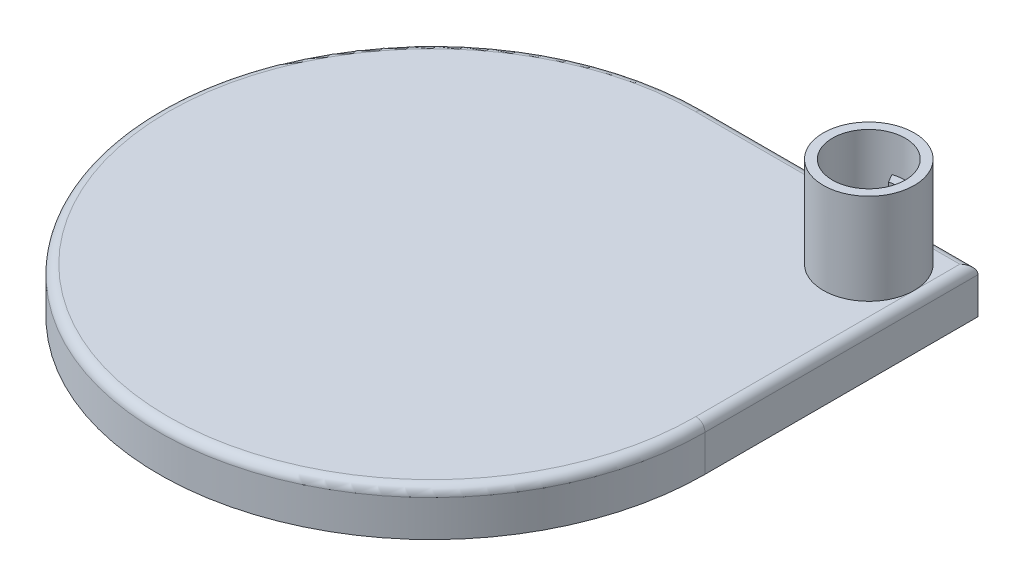
SolidWorks part; units mm, degrees
ref_plane "Front Plane" through (0, 0, 0) normal (0, 0, 1) x (1, 0, 0)
ref_plane "Top Plane" through (0, 0, 0) normal (0, 1, 0) x (1, 0, 0)
ref_plane "Right Plane" through (0, 0, 0) normal (1, 0, 0) x (0, 0, -1)
sketch "Sketch1" plane through (0, 0, 0) normal (0, 1, 0) x (1, 0, 0)
  line L1 (0, 0) -> (-38.1, 0)
  line L2 (0, 0) -> (0, -38.1)
  line L4 (-76.2, -38.1) -> (-76.2, -89.2737) construction
  arc A0 (-38.1, 0) -> (0, -38.1) centre (-38.1, -38.1) ccw
  dimension "D1" = 76.2
extrude "Boss-Extrude1" add sketch "Sketch1" along normal blind 6.35
sketch "Sketch2" plane through (0, 6.35, 0) normal (0, 1, 0) x (1, 0, 0)
  line L0 (0, -38.1) -> (0, 0) construction
  line L1 (0, 0) -> (-38.1, 0) construction
  circle A0 centre (-7.62, -7.62) radius 6.35
  circle A1 centre (-7.62, -7.62) radius 5.08
  dimension "D1" = 12.7
  dimension "D2" = 10.16
  dimension "D3" = 7.62
  dimension "D4" = 7.62
extrude "Boss-Extrude2" add sketch "Sketch2" along normal blind 12.7
sketch "Sketch3" plane through (0, 6.35, 0) normal (0, 1, 0) x (1, 0, 0)
  line L0 (-8.5634, -3.9287) -> (-9.2166, -2.7974)
  line L1 (-6.6766, -3.9287) -> (-6.0234, -2.7974)
  line L2 (-8.89, -3.363) -> (-6.35, -3.363) construction
  line L3 (-12.7, -7.62) -> (-2.54, -7.62) construction
  line L4 (-8.89, -11.877) -> (-6.35, -11.877) construction
  line L5 (-6.6766, -11.3113) -> (-6.0234, -12.4426)
  line L6 (-8.5634, -11.3113) -> (-9.2166, -12.4426)
  circle A0 centre (-7.62, -7.62) radius 5.08 construction
  circle A1 centre (-7.62, -7.62) radius 5.08
  circle A2 centre (-7.62, -7.62) radius 3.81
  circle M7 centre (-7.62, -7.62) radius 5.08
  dimension "D1" = 7.62
  dimension "D2" = 60
  dimension "D3" = 2.54
extrude "Boss-Extrude3" add sketch "Sketch3" along normal blind 2.54 from offset 5.08 contours A2 L1 L0 M7 | A2 L6 L5 M7 region at (-7.62, 6.35, 3.1843) region at (-7.62, 6.35, 12.0557)
fillet "Fillet1" radius 1.27 3 edges at (-19.05, 6.35, 0) (0, 6.35, 19.05) (-65.0408, 6.35, 65.0408)
